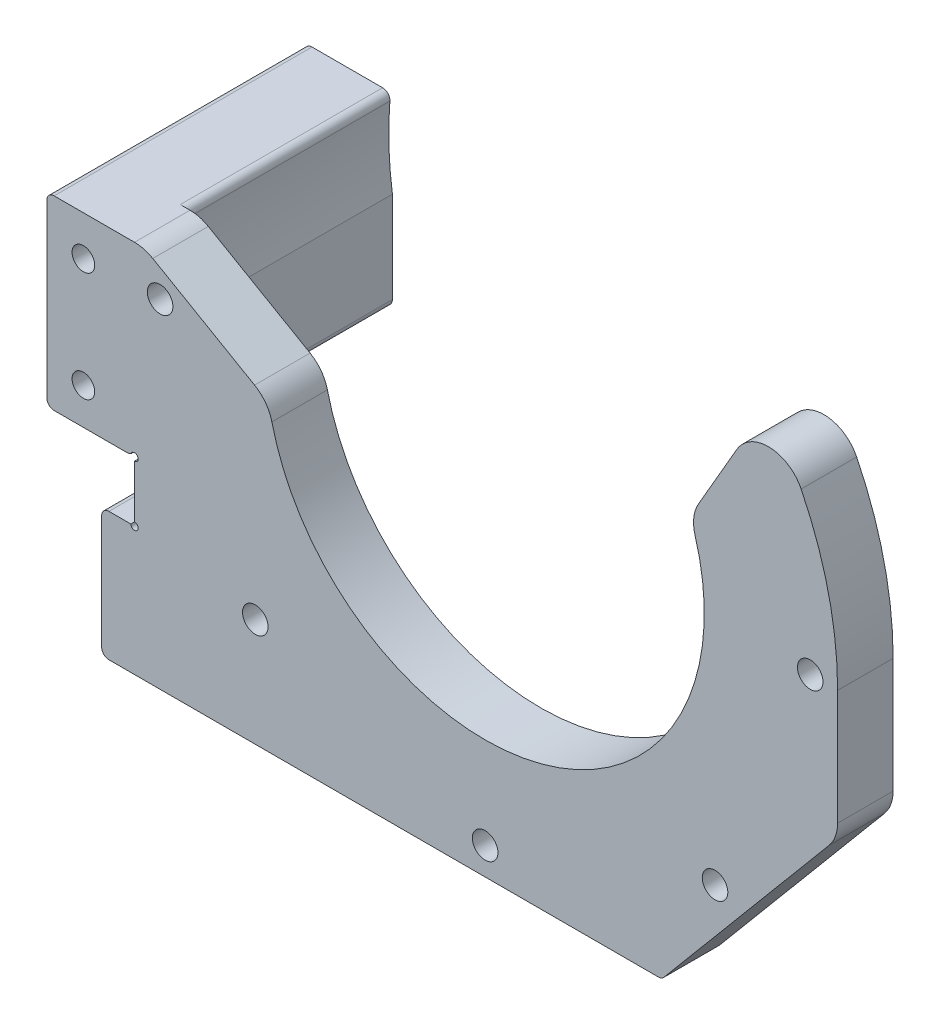
SolidWorks part; units mm, degrees
material "ABS"
ref_plane "前视基准面" through (0, 0, 0) normal (0, 0, 1) x (1, 0, 0)
ref_plane "上视基准面" through (0, 0, 0) normal (0, 1, 0) x (1, 0, 0)
ref_plane "右视基准面" through (0, 0, 0) normal (1, 0, 0) x (0, 0, -1)
other "Configuration Table"
sketch "草图1" plane through (0, 0, 0) normal (0, 0, 1) x (1, 0, 0)
  line L0 (0, 0) -> (0, -44.5) construction
  line L1 (0, 0) -> (-31.4663, -31.4663) construction
  line L3 (48.25, 0) -> (48.25, -17.5616)
  line L4 (24.1775, -46.25) -> (-52.5, -46.25)
  line L7 (-13.1909, -42.5) -> (13.1909, -42.5) construction
  line L8 (-13.7477, -46.25) -> (13.7477, -46.25) construction
  line L9 (-52.5, -46.25) -> (-60, -46.25)
  line L10 (-60, -46.25) -> (-60, 5) construction
  line L12 (-46.6603, 5) -> (-29.606, -4.8463)
  line L13 (-55, 5) -> (-55, -46.25) construction
  line L14 (-13.7477, 46.25) -> (13.7477, 46.25) construction
  line L15 (-44.5, 0) -> (44.5, 0) construction
  line L16 (-60, -20.45) -> (-48, -20.45)
  line L17 (-48, -20.45) -> (-48, -28.65)
  line L18 (-48, -28.65) -> (-60, -28.65)
  line L19 (0, -44.5) -> (0, -46.25) construction
  line L20 (24.1775, -46.25) -> (48.25, -17.5616)
  line L21 (-52.5, -28.65) -> (-52.5, -46.25)
  line L22 (-60, -20.45) -> (-60, 5)
  line L23 (28.0627, 10.606) -> (38.6303, 28.9096)
  line L24 (0, 0) -> (35.7484, 61.918) construction
  line L25 (35.7484, 61.918) -> (52.2028, 52.418) construction
  line L26 (52.2028, 52.418) -> (32.1509, 17.6871) construction
  line L27 (32.1509, 17.6871) -> (-0.758, 36.6871) construction
  line L28 (-0.758, 36.6871) -> (19.2939, 71.418) construction
  line L29 (19.2939, 71.418) -> (35.7484, 61.918) construction
  line L30 (0, 0) -> (-70.3526, 40.6181) construction
  line L31 (-70.3526, 40.6181) -> (-79.8526, 24.1636) construction
  line L32 (-79.8526, 24.1636) -> (-55.3788, 10.0337) construction
  line L33 (-55.3788, 10.0337) -> (-36.3788, 42.9426) construction
  line L34 (-36.3788, 42.9426) -> (-60.8526, 57.0726) construction
  line L35 (-60.8526, 57.0726) -> (-70.3526, 40.6181) construction
  line L36 (-60, 5) -> (-46.6603, 5)
  arc A0 (-29.606, -4.8463) -> (28.0627, 10.606) centre (0, 0) ccw
  circle A1 centre (0, 0) radius 44.5 construction
  circle A2 centre (-31.4663, -31.4663) radius 1.75
  circle A3 centre (0, -44.5) radius 1.75 construction
  circle A4 centre (31.4663, -31.4663) radius 1.75
  circle A5 centre (0, -42.5) radius 1.75
  circle A6 centre (0, 0) radius 48.25 construction
  circle A7 centre (-44.5, 0) radius 1.75
  circle A8 centre (44.5, 0) radius 1.75
  circle A12 centre (-55, -15.45) radius 1.55
  circle A13 centre (-55, -0.45) radius 1.55
  arc A14 (48.25, 0) -> (38.6303, 28.9096) centre (0, 0) ccw
  dimension "D2" = 89
  dimension "D3" = 60
  dimension "D4" = 3.5
  dimension "D6" = 42.5
  dimension "D8" = 96.5
  dimension "D13" = 5
  dimension "D14" = 38
  dimension "D19" = 60
  dimension "D23" = 7.5
  dimension "D24" = 15
  dimension "D10" = 3.1
  dimension "D1" = 45
  dimension "D5" = 30
  dimension "D7" = 5
  dimension "D9" = 92.5
  dimension "D11" = 51.25
  dimension "D15" = 17.6
  dimension "D16" = 8.2
  dimension "D17" = 12
  dimension "D18" = 60
  dimension "D20" = 50
extrude "凸台-拉伸1" add sketch "草图1" along normal blind 7.6 contours A0 L22 L16 L17 L18 L21 L9 L4 L20 L3 L23 A12 A8 A7 A5 A4 A2 region at (46.9322, -8.7808, 0)
sketch "草图2" plane through (0, 0, 0) normal (0, 0, -1) x (-1, 0, 0)
  circle A2 centre (48, -20.45) radius 0.5
  circle A3 centre (48, -28.65) radius 0.5
  dimension "D1" = 1
extrude "切除-拉伸1" cut sketch "草图2" against normal blind 10
fillet "圆角1" radius 5 5 edges at (48.25, -17.5616, 3.8) (28.0627, 10.606, 3.8) (-46.6603, 5, 3.8) (-29.606, -4.8463, 3.8) (38.6303, 28.9096, 3.8)
sketch "草图4" plane through (0, 0, 0) normal (0, 0, -1) x (-1, 0, 0)
  line L1 (60, 5) -> (48.2416, 5)
  line L2 (60, 5) -> (60, -20.45)
  line L3 (60, -20.45) -> (48, -20.45)
  line L4 (48, -6.9462) -> (48, -20.45)
  circle A0 centre (55, -15.45) radius 1.55 construction
  circle A1 centre (55, -0.45) radius 1.55 construction
  circle A2 centre (55, -15.45) radius 1.55
  circle A3 centre (55, -0.45) radius 1.55
  arc A4 (48, -6.9462) -> (48.2416, 5) centre (0, 0) ccw
  dimension "D1" = 97
extrude "凸台-拉伸2" add sketch "草图4" along normal blind 27.7
sketch "草图6" plane through (0, -20.45, 0) normal (0, -1, 0) x (1, 0, 0)
  line L0 (-48, 0) -> (-60, 0) construction
  line L1 (-48, 0) -> (-48.5, 0) construction
  line L2 (-48, -27.7) -> (-48, 0) construction
  line L3 (-60, 7.6) -> (-60, -27.7) construction
  line L4 (-55, 0) -> (-55, -27.7) construction
  line L6 (-55, -13.85) -> (-48, -13.85) construction
  circle A0 centre (-55, -21.35) radius 2.5
  circle A1 centre (-55, -6.35) radius 2.5
  dimension "D1" = 5
  dimension "D2" = 15
  dimension "D3" = 5
extrude "切除-拉伸2" cut sketch "草图6" against normal blind 5
fillet "圆角2" radius 1 7 edges at (24.1775, -46.25, 3.8) (-52.5, -46.25, 3.8) (-52.5, -28.65, 3.8) (-60, -20.45, -10.05) (-60, 5, -10.05) (-48, -20.45, -13.85) (-48.2416, 5, -13.85)
